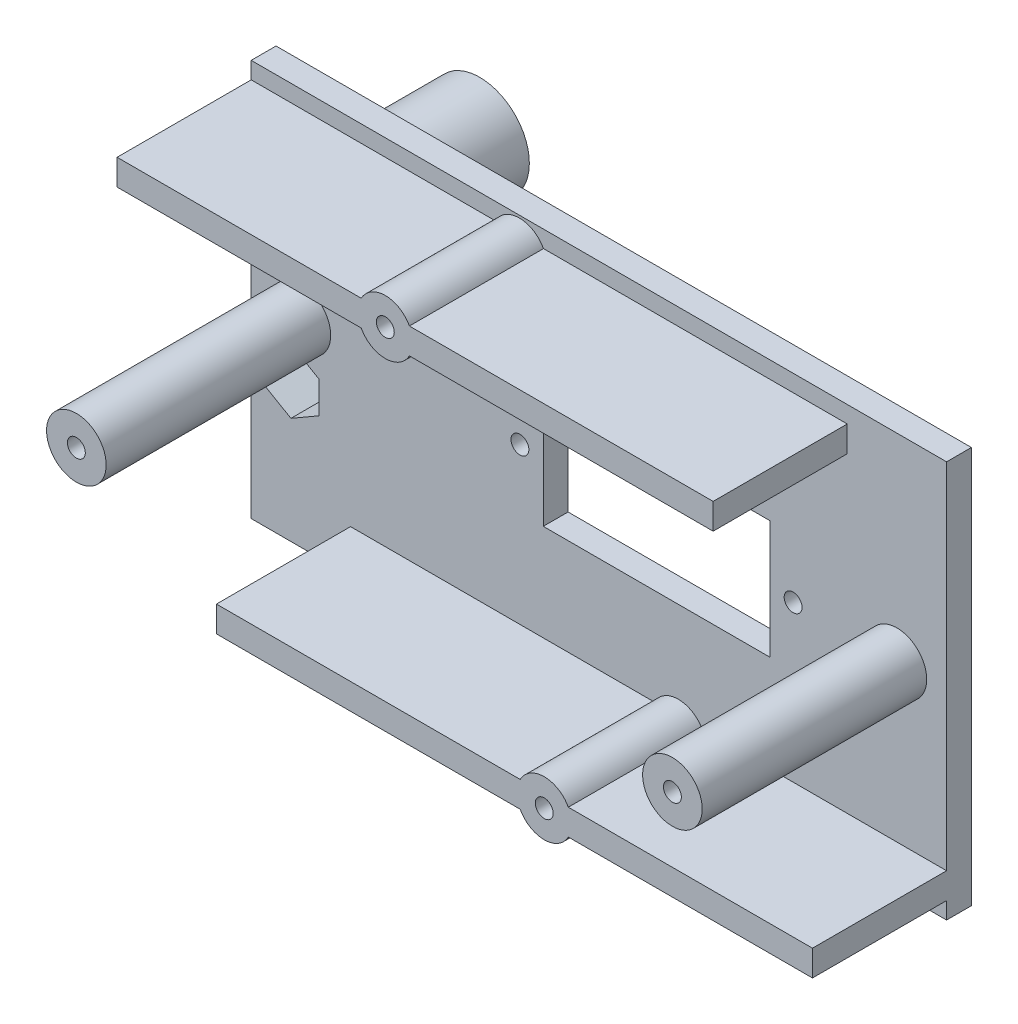
SolidWorks part; units mm, degrees
ref_plane "Front Plane" through (0, 0, 0) normal (0, 0, 1) x (1, 0, 0)
ref_plane "Top Plane" through (0, 0, 0) normal (0, 1, 0) x (1, 0, 0)
ref_plane "Right Plane" through (0, 0, 0) normal (1, 0, 0) x (0, 0, -1)
sketch "Sketch1" plane through (0, 0, 0) normal (0, 0, 1) x (1, 0, 0)
  line L0 (-35, -19.975) -> (35, -19.975)
  line L1 (35, -19.975) -> (35, 19.975)
  line L2 (35, 19.975) -> (-35, 19.975)
  line L3 (-35, 19.975) -> (-35, -19.975)
extrude "Boss-Extrude1" add sketch "Sketch1" along normal blind 2.5 from offset 2.5 offset against normal yes
sketch "Sketch2" plane through (0, 0, 0) normal (0, 0, 1) x (1, 0, 0)
  line L0 (-35, 15.675) -> (25, 15.675)
  line L1 (25, 15.675) -> (25, 18.275)
  line L2 (25, 18.275) -> (-35, 18.275)
  line L3 (-35, 18.275) -> (-35, 15.675)
extrude "Boss-Extrude2" add sketch "Sketch2" along normal blind 13.5
sketch "Sketch3" plane through (0, 0, 0) normal (0, 0, 1) x (1, 0, 0)
  line L0 (-25, -18.275) -> (35, -18.275)
  line L1 (35, -18.275) -> (35, -15.675)
  line L2 (35, -15.675) -> (-25, -15.675)
  line L3 (-25, -15.675) -> (-25, -18.275)
extrude "Boss-Extrude3" add sketch "Sketch3" along normal blind 13.5
sketch "Sketch4" plane through (0, 0, 0) normal (0, 0, 1) x (1, 0, 0)
  circle A0 centre (-8, 16.975) radius 2.75
  circle A1 centre (8, -16.975) radius 2.75
extrude "Boss-Extrude4" add sketch "Sketch4" along normal blind 13.5
sketch "Sketch5" plane through (0, 0, 0) normal (0, 0, 1) x (1, 0, 0)
  circle A0 centre (-31, 6) radius 5
  circle A1 centre (-31, -6) radius 5
extrude "Boss-Extrude5" add sketch "Sketch5" along normal blind 16.5 from offset 19 offset against normal yes
sketch "Sketch6" plane through (0, 0, 0) normal (0, 0, 1) x (1, 0, 0)
  circle A0 centre (30, 0) radius 3
  circle A1 centre (-30, 0) radius 3
extrude "Boss-Extrude6" add sketch "Sketch6" along normal blind 22.6
sketch "Sketch7" plane through (0, 0, 0) normal (0, 0, 1) x (1, 0, 0)
  circle A0 centre (30, 0) radius 0.9
  circle A1 centre (-30, 0) radius 0.9
extrude "Cut-Extrude1" cut sketch "Sketch7" along normal blind 8.1 from offset 14.6
sketch "Sketch8" plane through (0, 0, 0) normal (0, 0, 1) x (1, 0, 0)
  line L0 (-5.6, -5.95) -> (17.2, -5.95)
  line L1 (17.2, -5.95) -> (17.2, 5.95)
  line L2 (17.2, 5.95) -> (-5.6, 5.95)
  line L3 (-5.6, 5.95) -> (-5.6, -5.95)
extrude "Cut-Extrude2" cut sketch "Sketch8" against normal through all and the other way through all
sketch "Sketch9" plane through (0, 0, 0) normal (0, 0, 1) x (1, 0, 0)
  circle A0 centre (-7.95, 0) radius 0.9
  circle A1 centre (19.55, 0) radius 0.9
extrude "Cut-Extrude3" cut sketch "Sketch9" against normal through all and the other way through all
sketch "Sketch10" plane through (0, 0, 0) normal (0, 0, 1) x (1, 0, 0)
  circle A0 centre (-8, 16.975) radius 0.9
  circle A1 centre (8, -16.975) radius 0.9
extrude "Cut-Extrude4" cut sketch "Sketch10" against normal through all and the other way through all
sketch "Sketch11" plane through (0, 0, 0) normal (0, 0, 1) x (1, 0, 0)
  circle A0 centre (-31, 6) radius 1.725
  circle A1 centre (-31, -6) radius 1.725
extrude "Cut-Extrude5" cut sketch "Sketch11" against normal through all and the other way through all
sketch "Sketch12" plane through (0, 0, 0) normal (0, 0, 1) x (1, 0, 0)
  line L0 (-28.2, 7.6166) -> (-31, 9.2332)
  line L1 (-31, 9.2332) -> (-33.8, 7.6166)
  line L2 (-33.8, 7.6166) -> (-33.8, 4.3834)
  line L3 (-33.8, 4.3834) -> (-31, 2.7668)
  line L4 (-31, 2.7668) -> (-28.2, 4.3834)
  line L5 (-28.2, 4.3834) -> (-28.2, 7.6166)
  line L6 (-28.2, -4.3834) -> (-31, -2.7668)
  line L7 (-31, -2.7668) -> (-33.8, -4.3834)
  line L8 (-33.8, -4.3834) -> (-33.8, -7.6166)
  line L9 (-33.8, -7.6166) -> (-31, -9.2332)
  line L10 (-31, -9.2332) -> (-28.2, -7.6166)
  line L11 (-28.2, -7.6166) -> (-28.2, -4.3834)
extrude "Cut-Extrude6" cut sketch "Sketch12" along normal blind 4.2 from offset 4.2 offset against normal yes
